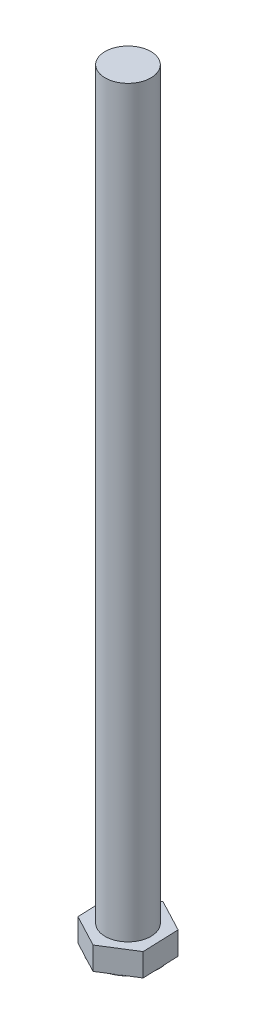
SolidWorks part; units mm, degrees
ref_plane "Front Plane" through (0, 0, 0) normal (0, 0, 1) x (1, 0, 0)
ref_plane "Top Plane" through (0, 0, 0) normal (0, 1, 0) x (1, 0, 0)
ref_plane "Right Plane" through (0, 0, 0) normal (1, 0, 0) x (0, 0, -1)
sketch "Sketch1" plane through (0, 0, 0) normal (0, 1, 0) x (1, 0, 0)
  line L1 (5.6147, -2.9678) -> (5.3776, 3.3786)
  line L2 (5.3776, 3.3786) -> (-0.2372, 6.3464)
  line L3 (-0.2372, 6.3464) -> (-5.6147, 2.9678)
  line L4 (-5.6147, 2.9678) -> (-5.3776, -3.3786)
  line L5 (-5.3776, -3.3786) -> (0.2372, -6.3464)
  line L6 (0.2372, -6.3464) -> (5.6147, -2.9678)
  circle A1 centre (0, 0) radius 5.5 construction
extrude "Boss-Extrude1" add sketch "Sketch1" along normal blind 4
sketch "Sketch2" plane through (0, 0, 0) normal (0, -1, 0) x (-1, 0, 0)
  circle A0 centre (0, 0) radius 5.5
extrude "Boss-Extrude2" add sketch "Sketch2" along normal blind 0.1
fillet "Fillet3" radius 0.1 6 edges at (4.6571, 0, -2.926) (4.8625, 0, 2.5702) (0.2054, 0, 5.4962) (-4.6571, 0, 2.926) (-4.8625, 0, -2.5702) (-0.2054, 0, -5.4962)
sketch "Sketch3" plane through (0, 4, 0) normal (0, 1, 0) x (1, 0, 0)
  circle A0 centre (0, 0) radius 4
extrude "Boss-Extrude3" add sketch "Sketch3" along normal blind 130
